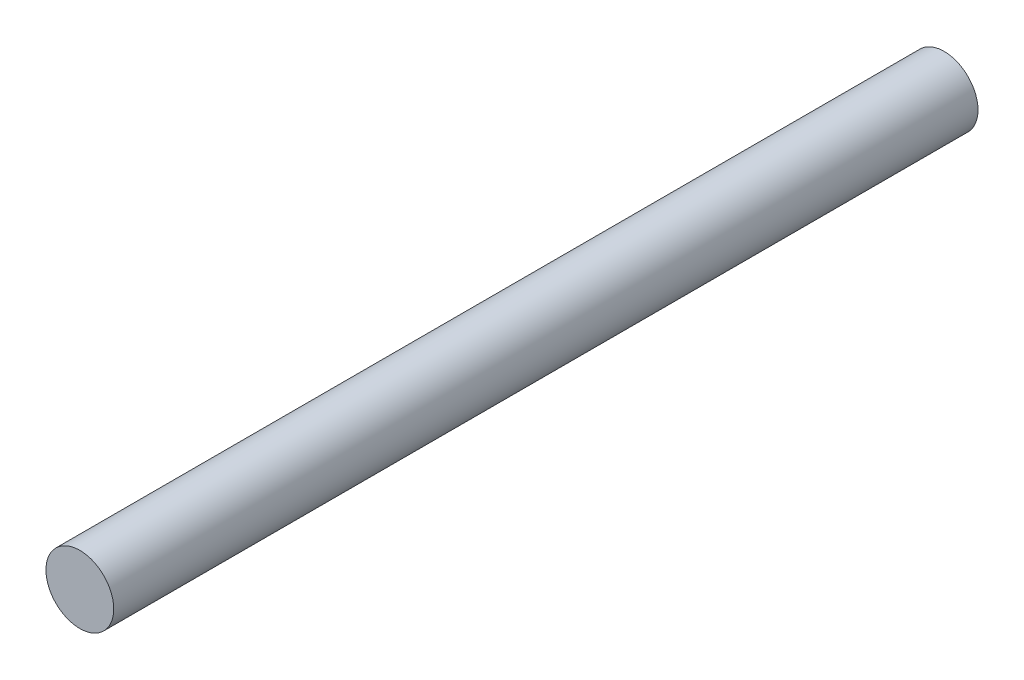
SolidWorks part; units mm, degrees
ref_plane "Front Plane" through (0, 0, 0) normal (0, 0, 1) x (1, 0, 0)
ref_plane "Top Plane" through (0, 0, 0) normal (0, 1, 0) x (1, 0, 0)
ref_plane "Right Plane" through (0, 0, 0) normal (1, 0, 0) x (0, 0, -1)
sketch "Sketch1" plane through (0, 0, 0) normal (0, 0, 1) x (1, 0, 0)
  circle A0 centre (0, 0) radius 20
  point P3 (0, 0)
  dimension "D1" = 40
extrude "Boss-Extrude1" add sketch "Sketch1" along normal blind 510 contours A0
